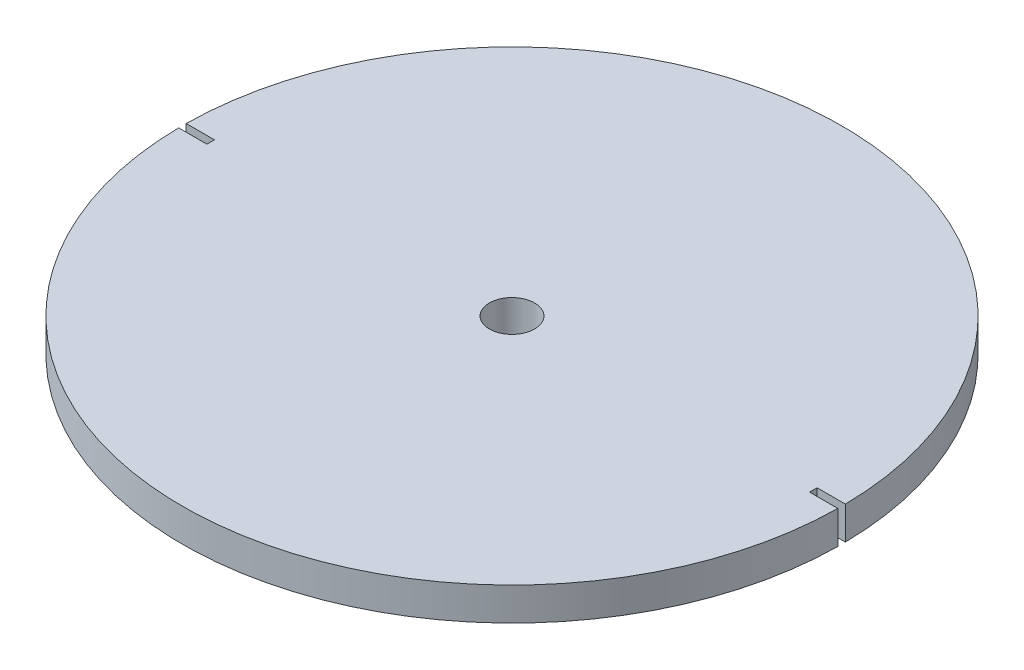
SolidWorks part; units mm, degrees
ref_plane "정면" through (0, 0, 0) normal (0, 0, 1) x (1, 0, 0)
ref_plane "윗면" through (0, 0, 0) normal (0, 1, 0) x (1, 0, 0)
ref_plane "우측면" through (0, 0, 0) normal (1, 0, 0) x (0, 0, -1)
sketch "스케치1" plane through (0, 0, 0) normal (0, 1, 0) x (1, 0, 0)
  line L9 (6.4741, -15.6298) -> (15.6298, -6.4741)
  line L18 (8.706, -21.0183) -> (21.0183, -8.706)
  line L19 (21.0183, -8.706) -> (21.0183, 8.706)
  line L20 (21.0183, 8.706) -> (8.706, 21.0183)
  line L21 (8.706, 21.0183) -> (-8.706, 21.0183)
  line L22 (-8.706, 21.0183) -> (-21.0183, 8.706)
  line L23 (-21.0183, 8.706) -> (-21.0183, -8.706)
  line L24 (-21.0183, -8.706) -> (-8.706, -21.0183)
  line L25 (-8.706, -21.0183) -> (8.706, -21.0183)
  line L26 (-10.7151, -25.8686) -> (10.7151, -25.8686)
  line L27 (10.7151, -25.8686) -> (25.8686, -10.7151)
  line L28 (25.8686, -10.7151) -> (25.8686, 10.7151)
  line L29 (25.8686, 10.7151) -> (10.7151, 25.8686)
  line L30 (10.7151, 25.8686) -> (-10.7151, 25.8686)
  line L31 (-10.7151, 25.8686) -> (-25.8686, 10.7151)
  line L32 (-25.8686, 10.7151) -> (-25.8686, -10.7151)
  line L33 (-25.8686, -10.7151) -> (-10.7151, -25.8686)
  line L34 (6.8883, -16.6298) -> (16.6298, -6.8883)
  line L35 (16.6298, -6.8883) -> (16.6298, 6.8883)
  line L36 (16.6298, 6.8883) -> (6.8883, 16.6298)
  line L37 (6.8883, 16.6298) -> (-6.8883, 16.6298)
  line L38 (-6.8883, 16.6298) -> (-16.6298, 6.8883)
  line L39 (-16.6298, 6.8883) -> (-16.6298, -6.8883)
  line L40 (-16.6298, -6.8883) -> (-6.8883, -16.6298)
  line L41 (-6.8883, -16.6298) -> (6.8883, -16.6298)
  line L42 (15.6298, -6.4741) -> (15.6298, 6.4741)
  line L43 (15.6298, 6.4741) -> (6.4741, 15.6298)
  line L44 (6.4741, 15.6298) -> (-6.4741, 15.6298)
  line L45 (-6.4741, 15.6298) -> (-15.6298, 6.4741)
  line L46 (-15.6298, 6.4741) -> (-15.6298, -6.4741)
  line L47 (-15.6298, -6.4741) -> (-6.4741, -15.6298)
  line L48 (-6.4741, -15.6298) -> (6.4741, -15.6298)
  line L49 (-10.3009, -24.8686) -> (10.3009, -24.8686)
  line L50 (10.3009, -24.8686) -> (24.8686, -10.3009)
  line L51 (24.8686, -10.3009) -> (24.8686, 10.3009)
  line L52 (24.8686, 10.3009) -> (10.3009, 24.8686)
  line L53 (10.3009, 24.8686) -> (-10.3009, 24.8686)
  line L54 (-10.3009, 24.8686) -> (-24.8686, 10.3009)
  line L55 (-24.8686, 10.3009) -> (-24.8686, -10.3009)
  line L56 (-24.8686, -10.3009) -> (-10.3009, -24.8686)
  line L57 (8.2918, -20.0183) -> (20.0183, -8.2918)
  line L58 (20.0183, -8.2918) -> (20.0183, 8.2918)
  line L59 (20.0183, 8.2918) -> (8.2918, 20.0183)
  line L60 (8.2918, 20.0183) -> (-8.2918, 20.0183)
  line L61 (-8.2918, 20.0183) -> (-20.0183, 8.2918)
  line L62 (-20.0183, 8.2918) -> (-20.0183, -8.2918)
  line L63 (-20.0183, -8.2918) -> (-8.2918, -20.0183)
  line L64 (-8.2918, -20.0183) -> (8.2918, -20.0183)
  line L81 (12.2143, -29.488) -> (29.488, -12.2143)
  line L82 (12.6286, -30.488) -> (30.488, -12.6286)
  line L83 (30.488, -12.6286) -> (30.488, 12.6286)
  line L84 (30.488, 12.6286) -> (12.6286, 30.488)
  line L85 (12.6286, 30.488) -> (-12.6286, 30.488)
  line L86 (-12.6286, 30.488) -> (-30.488, 12.6286)
  line L87 (-30.488, 12.6286) -> (-30.488, -12.6286)
  line L88 (-30.488, -12.6286) -> (-12.6286, -30.488)
  line L89 (-12.6286, -30.488) -> (12.6286, -30.488)
  line L90 (29.488, -12.2143) -> (29.488, 12.2143)
  line L91 (29.488, 12.2143) -> (12.2143, 29.488)
  line L92 (12.2143, 29.488) -> (-12.2143, 29.488)
  line L93 (-12.2143, 29.488) -> (-29.488, 12.2143)
  line L94 (-29.488, 12.2143) -> (-29.488, -12.2143)
  line L95 (-29.488, -12.2143) -> (-12.2143, -29.488)
  line L96 (-12.2143, -29.488) -> (12.2143, -29.488)
  circle A2 centre (0, 0) radius 22.75 construction
  circle A3 centre (0, 0) radius 28 construction
  circle A4 centre (0, 0) radius 18 construction
  circle A5 centre (0, 0) radius 33 construction
  point P1 (0, 0)
  dimension "D3" = 45.5
  dimension "D4" = 56
  dimension "D5" = 36
  dimension "D11" = 66
  dimension "D6" = 1
  dimension "D7" = 1
  dimension "D8" = 1
  dimension "D12" = 1
sketch "스케치3" plane through (0, 0, 0) normal (0, 1, 0) x (1, 0, 0)
  circle A1 centre (0, 0) radius 35
  dimension "D1" = 70
extrude "보스-돌출1" add sketch "스케치3" along normal blind 3.5
extrude "컷-돌출5" cut sketch "스케치1" along normal blind 1.2 contours L40 L41 L34 L35 L36 L37 L38 L39 L48 L47 L46 L45 L44 L43 L42 L9 | L32 L33 L26 L27 L28 L29 L30 L31 L56 L55 L54 L53 L52 L51 L50 L49 | L24 L25 L18 L19 L20 L21 L22 L23 L64 L63 L62 L61 L60 L59 L58 L57 | L88 L89 L82 L83 L84 L85 L86 L87 L96 L95 L94 L93 L92 L91 L90 L81 region at (0, 0, 20.4238) region at (-17.7745, 0, 17.7745) region at (0, 0, 16.1595) region at (0, 0, 29.6257)
sketch "스케치4" plane through (0, 3.5, 0) normal (0, 1, 0) x (1, 0, 0)
  line L0 (-37, 0) -> (-32, 0) construction
  line L1 (-37, 0.4) -> (-32, 0.4)
  line L2 (-37, 0.4) -> (-37, -0.4)
  line L3 (-37, -0.4) -> (-32, -0.4)
  line L4 (-32, 0.4) -> (-32, -0.4)
  line L5 (0, -1.925) -> (0, 1.925) construction
  line L6 (-1.925, 0) -> (1.925, 0) construction
  line L7 (37, -0.4) -> (32, -0.4)
  line L8 (32, 0.4) -> (32, -0.4)
  line L9 (37, 0.4) -> (32, 0.4)
  line L10 (37, 0.4) -> (37, -0.4)
  dimension "D1" = 5
  dimension "D2" = 0.8
  dimension "D3" = 37
extrude "컷-돌출6" cut sketch "스케치4" against normal through all
sketch "스케치5" plane through (0, 3.5, 0) normal (0, 1, 0) x (1, 0, 0)
  circle A0 centre (0, 0) radius 2.4
  dimension "D1" = 4.8
extrude "컷-돌출7" cut sketch "스케치5" against normal through all
